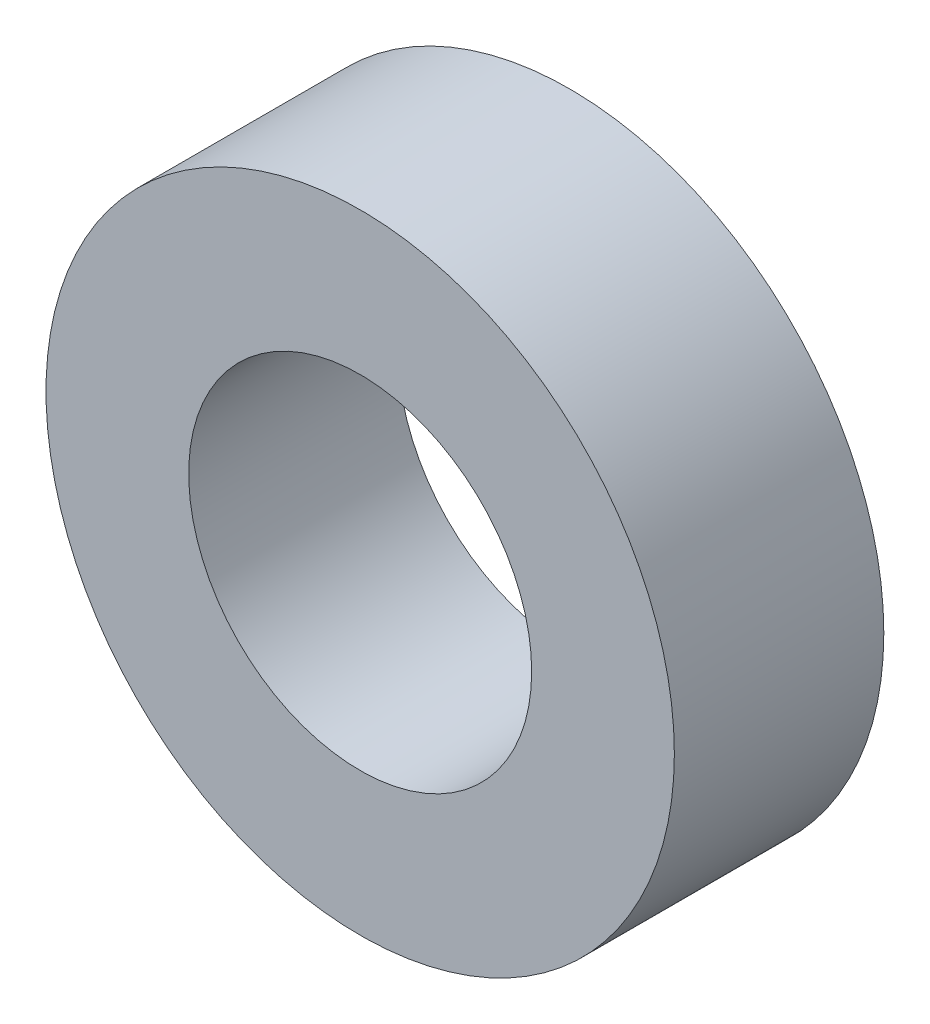
SolidWorks part; units mm, degrees
ref_plane "Front Plane" through (0, 0, 0) normal (0, 0, 1) x (1, 0, 0)
ref_plane "Top Plane" through (0, 0, 0) normal (0, 1, 0) x (1, 0, 0)
ref_plane "Right Plane" through (0, 0, 0) normal (1, 0, 0) x (0, 0, -1)
sketch "Sketch1" plane through (0, 0, 0) normal (0, 0, 1) x (1, 0, 0)
  circle A0 centre (0, 0) radius 1.6375
  circle A1 centre (0, 0) radius 3
  dimension "D1" = 3.275
  dimension "D2" = 6
extrude "Boss-Extrude1" add sketch "Sketch1" along normal blind 2
